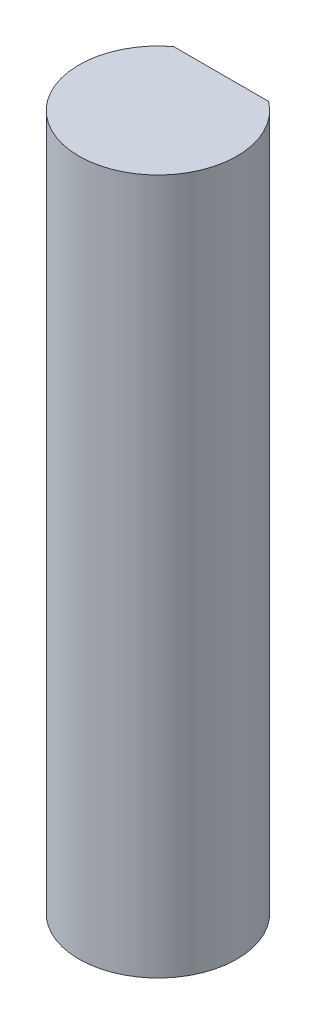
SolidWorks part; units mm, degrees
ref_plane "Front Plane" through (0, 0, 0) normal (0, 0, 1) x (1, 0, 0)
ref_plane "Top Plane" through (0, 0, 0) normal (0, 1, 0) x (1, 0, 0)
ref_plane "Right Plane" through (0, 0, 0) normal (1, 0, 0) x (0, 0, -1)
sketch "Sketch2" plane through (0, 0, 0) normal (0, 1, 0) x (1, 0, 0)
  line L0 (0, -2.5) -> (0, 2) construction
  line L1 (-1.5, 2) -> (1.5, 2)
  circle A0 centre (0, 0) radius 2.5
  dimension "D1" = 5
  dimension "D2" = 4.5
extrude "Boss-Extrude1" add sketch "Sketch2" along normal blind 22 contours L0 A0 L1 | A0 L0 L1 region at (-1.0879, 0, 0.1209) region at (1.0879, 0, 0.1209)
extrude "Boss-Extrude2" add sketch "Sketch2<3>" along normal blind 4 contours L1 A0 region at (0, 0, -2.2018)
sketch "Sketch2<3>" plane through (0, 0, 0) normal (0, 1, 0) x (1, 0, 0) same geometry as "Sketch2"
